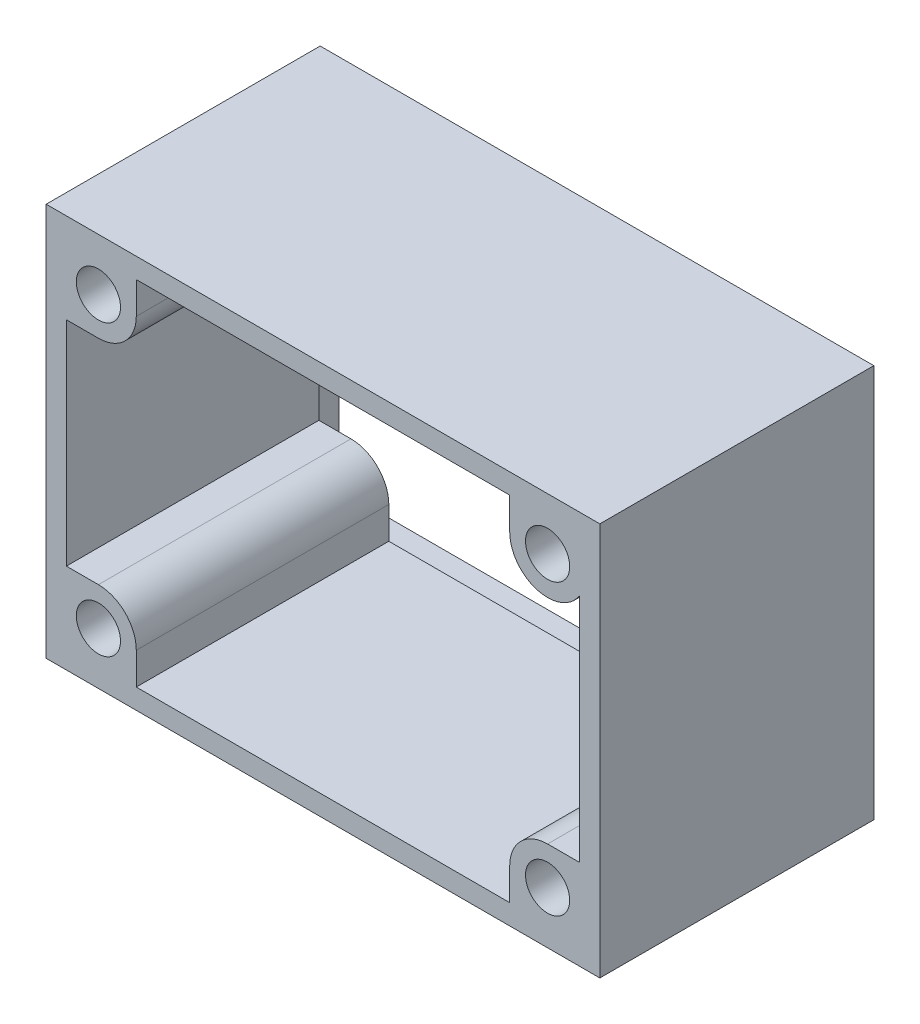
SolidWorks part; units mm, degrees
ref_plane "Front Plane" through (0, 0, 0) normal (0, 0, 1) x (1, 0, 0)
ref_plane "Top Plane" through (0, 0, 0) normal (0, 1, 0) x (1, 0, 0)
ref_plane "Right Plane" through (0, 0, 0) normal (1, 0, 0) x (0, 0, -1)
sketch "Sketch1" plane through (0, 0, 0) normal (0, 0, 1) x (1, 0, 0)
  line L0 (-20.325, 13.975) -> (-20.325, 15.575) construction
  line L1 (-21.925, -15.575) -> (21.925, -15.575)
  line L2 (-21.925, -15.575) -> (-21.925, 15.575)
  line L3 (-21.925, 15.575) -> (21.925, 15.575)
  line L4 (20.325, -13.975) -> (20.325, 13.975)
  line L5 (20.325, 13.975) -> (-20.325, 13.975)
  line L6 (-20.325, 13.975) -> (-20.325, -13.975)
  line L7 (-20.325, -13.975) -> (20.325, -13.975)
  line L8 (20.325, -13.975) -> (20.325, 13.975)
  line L9 (20.325, 13.975) -> (-20.325, 13.975)
  line L10 (-20.325, 13.975) -> (-20.325, -13.975)
  line L11 (-20.325, -13.975) -> (20.325, -13.975)
  line L12 (21.925, -15.575) -> (21.925, 15.575)
  line L13 (-21.925, -15.575) -> (21.925, 15.575) construction
  line L14 (-21.925, 15.575) -> (21.925, -15.575) construction
  line L15 (-20.325, 13.975) -> (-21.925, 13.975) construction
  line L16 (-14.7875, 11.45) -> (-14.7875, 13.975)
  line L17 (-17.7875, 8.45) -> (-20.325, 8.45)
  line L18 (0, 15.575) -> (0, -15.575) construction
  line L19 (-21.925, 0) -> (21.925, 0) construction
  line L20 (14.7875, 11.45) -> (14.7875, 13.975)
  line L21 (17.7875, 8.45) -> (20.325, 8.45)
  line L22 (17.7875, -8.45) -> (20.325, -8.45)
  line L23 (14.7875, -11.45) -> (14.7875, -13.975)
  line L24 (-14.7875, -11.45) -> (-14.7875, -13.975)
  line L25 (-17.7875, -8.45) -> (-20.325, -8.45)
  circle A0 centre (-17.7875, 11.45) radius 1.75
  circle A1 centre (17.7875, 11.45) radius 3
  circle A2 centre (17.7875, -11.45) radius 3
  circle A3 centre (-17.7875, -11.45) radius 3
  circle A4 centre (-17.7875, 11.45) radius 3
  circle A5 centre (17.7875, 11.45) radius 1.75
  circle A6 centre (17.7875, -11.45) radius 1.75
  circle A7 centre (-17.7875, -11.45) radius 1.75
  point P16 (0, 0)
  point P33 (-19.0562, 8.45)
  point P44 (-19.0562, -8.45)
  dimension "D2" = 3.5
  dimension "D4" = 6
  dimension "D3" = 1.6
  dimension "D1" = 0
extrude "Boss-Extrude1" add sketch "Sketch1" along normal blind 20 contours L9 A4 L10 A0 | A4 L10 L17 | A4 L16 L9 | L9 A4 | L10 A4 | L1 L12 L3 L2 A4 L9 A1 L8 A2 L11 A3 L10 | A4 L9 L10 | L9 A1 L8 | A1 L8 | L20 A1 L9 | A1 L8 L9 A5 | A1 L9 | A2 L11 L8 | L8 A2 L11 A6 | L8 A2 | L11 A2 | A2 L23 L11 | A2 L8 L22 | L11 A3 L10 | A3 L10 | A3 L11 | A3 L11 L10 A7 | L24 A3 L11 | L10 A3 L25 region at (-21.3871, 0, 0) region at (19.724, -8.8454, 0) region at (20.5113, -11.45, 0) region at (20.2468, -11.45, 0) region at (19.1987, 8.8916, 0) region at (20.5113, 11.45, 0) region at (20.042, -13.6898, 0) region at (15.1778, -13.3764, 0) region at (20.042, 13.6898, 0) region at (15.1778, 13.3764, 0) region at (17.7875, -14.1664, 0) region at (17.7875, 14.1664, 0) region at (-15.1778, -13.3764, 0) region at (-15.1778, 13.3764, 0) region at (-17.7875, -14.1664, 0) region at (-17.7875, -13.8968, 0) region at (-15.2237, 12.8512, 0) region at (-17.7875, 14.1664, 0) region at (-20.042, -13.6898, 0) region at (-19.724, -8.8454, 0) region at (-20.042, 13.6898, 0) region at (-19.724, 8.8454, 0) region at (-20.5113, -11.45, 0) region at (-20.5113, 11.45, 0)
sketch "Sketch2" plane through (0, 0, 0) normal (0, 0, -1) x (-1, 0, 0)
  line L0 (21.925, -15.575) -> (-21.925, 15.575) construction
  line L2 (-20.425, 14.075) -> (20.425, 14.075)
  line L3 (-20.425, 14.075) -> (-20.425, -14.075)
  line L4 (-21.925, -15.575) -> (21.925, -15.575)
  line L5 (21.925, -15.575) -> (21.925, 15.575)
  line L6 (21.925, 15.575) -> (-21.925, 15.575)
  line L7 (-21.925, 15.575) -> (-21.925, -15.575)
  line L8 (-21.925, -15.575) -> (21.925, -15.575)
  line L9 (21.925, -15.575) -> (21.925, 15.575)
  line L10 (21.925, 15.575) -> (-21.925, 15.575)
  line L11 (-21.925, 15.575) -> (-21.925, -15.575)
  line L12 (-20.425, -14.075) -> (20.425, -14.075)
  line L13 (20.425, 14.075) -> (20.425, -14.075)
  line L14 (-20.425, 14.075) -> (20.425, -14.075) construction
  line L15 (-20.425, -14.075) -> (20.425, 14.075) construction
  line L16 (-20.425, 14.075) -> (-21.925, 14.075) construction
  line L17 (-20.425, 14.075) -> (-20.425, 15.575) construction
  point P2 (0, 0)
  point P9 (0, 0)
  dimension "D2" = 1.5
  dimension "D1" = 0
extrude "Boss-Extrude2" add sketch "Sketch2" along normal blind 1.7
